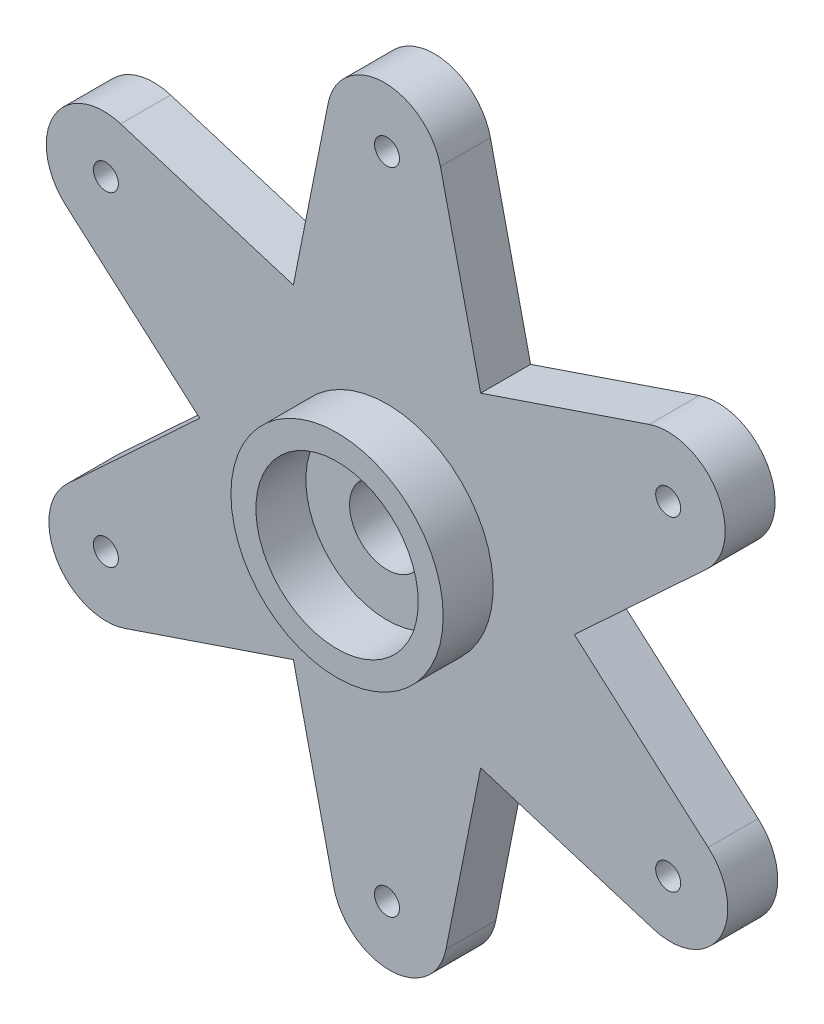
SolidWorks part; units mm, degrees
ref_plane "Plano frontal" through (0, 0, 0) normal (0, 0, 1) x (1, 0, 0)
ref_plane "Plano superior" through (0, 0, 0) normal (0, 1, 0) x (1, 0, 0)
ref_plane "Plano direito" through (0, 0, 0) normal (1, 0, 0) x (0, 0, -1)
sketch "Esboço1" plane through (0, 0, 0) normal (0, 0, 1) x (1, 0, 0)
  line L0 (3.75, 6.4952) -> (2.1402, 13.5512)
  line L1 (-3.75, 6.4952) -> (-2.3598, 13.4881)
  line L2 (7.5, 0) -> (12.8058, 4.9221)
  line L3 (3.75, 6.4952) -> (10.5011, 8.7877)
  line L4 (3.75, -6.4952) -> (10.6656, -8.6291)
  line L5 (7.5, 0) -> (12.8609, -4.7004)
  line L6 (-3.75, -6.4952) -> (-2.1402, -13.5512)
  line L7 (3.75, -6.4952) -> (2.3598, -13.4881)
  line L8 (-7.5, 0) -> (-12.8058, -4.9221)
  line L9 (-3.75, -6.4952) -> (-10.5011, -8.7877)
  line L10 (-3.75, 6.4952) -> (-10.6656, 8.6291)
  line L11 (-7.5, 0) -> (-12.8609, 4.7004)
  arc A1 (-2.3598, 13.4881) -> (2.1402, 13.5512) centre (-0.1031, 13.0394) cw
  arc A2 (10.5011, 8.7877) -> (12.8058, 4.9221) centre (11.2409, 6.609) cw
  arc A3 (12.8609, -4.7004) -> (10.6656, -8.6291) centre (11.344, -6.4305) cw
  arc A4 (2.3598, -13.4881) -> (-2.1402, -13.5512) centre (0.1031, -13.0394) cw
  arc A5 (-10.5011, -8.7877) -> (-12.8058, -4.9221) centre (-11.2409, -6.609) cw
  arc A6 (-12.8609, 4.7004) -> (-10.6656, 8.6291) centre (-11.344, 6.4305) cw
  circle A7 centre (0, 0) radius 1.5
  point P9 (0, 0)
  point P36 (0, 0)
  dimension "D2" = 7.5
  dimension "D5" = 3
  dimension "D3" = 4.5
  dimension "D4" = 6
extrude "Ressalto-extrusão1" add sketch "Esboço1" along normal mid plane 2
sketch "Esboço2" plane through (0, 0, 1) normal (0, 0, 1) x (1, 0, 0)
  circle A0 centre (0, 0) radius 4.25
  circle A1 centre (0, 0) radius 3.25
  dimension "D1" = 8.5
  dimension "D2" = 6.5
extrude "Ressalto-extrusão2" add sketch "Esboço2" along normal blind 2
sketch "Esboço3" plane through (0, 0, 1) normal (0, 0, 1) x (1, 0, 0)
  circle A0 centre (0, 0) radius 13
  circle A1 centre (0, 13) radius 0.5
  circle A2 centre (11.2583, 6.5) radius 0.5
  circle A3 centre (11.2583, -6.5) radius 0.5
  circle A4 centre (0, -13) radius 0.5
  circle A5 centre (-11.2583, -6.5) radius 0.5
  circle A6 centre (-11.2583, 6.5) radius 0.5
  point P17 (0, 0)
  dimension "D1" = 1
  dimension "D2" = 26
  dimension "D3" = 6
extrude "Corte-extrusão1" cut sketch "Esboço3" against normal blind 2 contours A1 | A6 | A5 | A4 | A3 | A2
